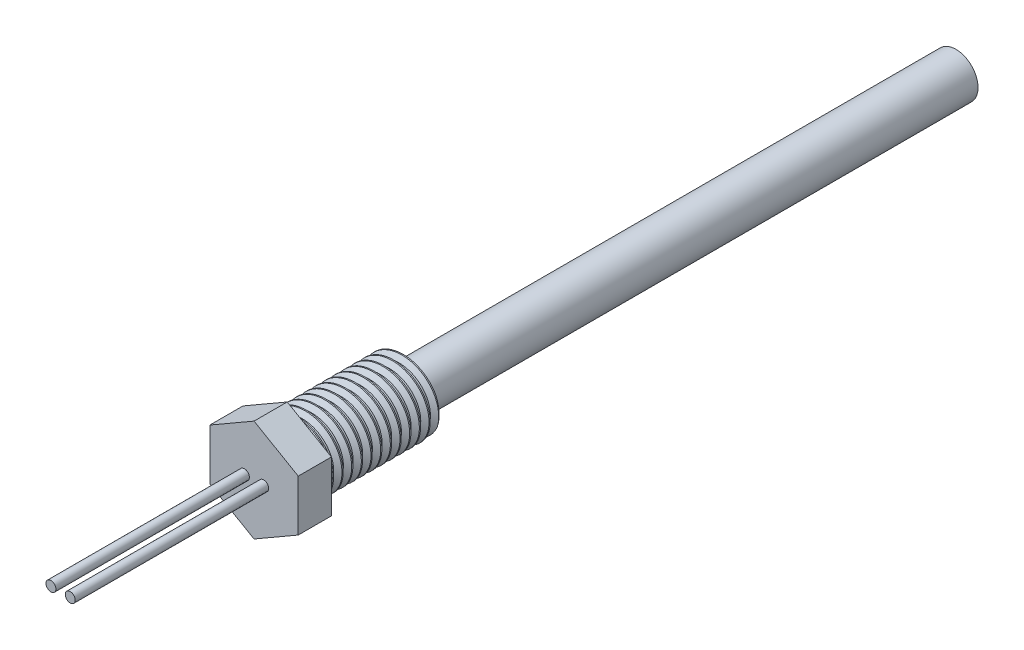
SolidWorks part; units mm, degrees
ref_plane "Ön Düzlem" through (0, 0, 0) normal (0, 0, 1) x (1, 0, 0)
ref_plane "Üst Düzlem" through (0, 0, 0) normal (0, 1, 0) x (1, 0, 0)
ref_plane "Sağ Düzlem" through (0, 0, 0) normal (1, 0, 0) x (0, 0, -1)
sketch "Çizim1" plane through (0, 0, 0) normal (0, 0, 1) x (1, 0, 0)
  circle A0 centre (0, 0) radius 4
  dimension "D1" = 8
extrude "Yükseklik-Ekstrüzyon1" add sketch "Çizim1" along normal blind 150
sketch "Çizim2" plane through (0, 0, 150) normal (0, 0, 1) x (1, 0, 0)
  circle A0 centre (0, 0) radius 6.5
  dimension "D1" = 13
extrude "Yükseklik-Ekstrüzyon2" add sketch "Çizim2" along normal blind 27
thread "Diş1" pitch 1.75 method cut profile "Diş Profili1" start angle 0, offset 0, length 30, pitch 1.75, diameter 13
ref_plane "Düzlem1" through (-6.5, 0, 177) normal (0, -1, 0) x (-1, 0, 0)
sketch "Diş Profili1" plane through (-6.5, 0, 177) normal (0, -1, 0) x (-1, 0, 0)
  line L0 (0, 0) -> (0, 1.75) construction
  line L11 (0, 0) -> (0, 1.5312)
  line L12 (0, 1.5312) -> (-0.9472, 0.9844)
  line L13 (-0.9472, 0.9844) -> (-0.9472, 0.5469)
  line L15 (-0.9472, 0.5469) -> (0, 0)
  line L17 (-0.9472, 0.7656) -> (0, 0.7656) construction
  point P2 (0, 0)
  dimension "Pitch" = 1.75
  dimension "Profile_Angle" = 60
  dimension "Profile_Land" = 0.4375
  dimension "Profile_Height" = 0.9472
sketch "Çizim3" plane through (0, 0, 0) normal (0, 0, -1) x (-1, 0, 0)
  circle A0 centre (0, 0) radius 13.0253
extrude "Kes-Ekstrüzyon1" cut sketch "Çizim3" against normal blind 50
sketch "Çizim5" plane through (0, 0, 177) normal (0, 0, 1) x (1, 0, 0)
  line L1 (0, -9.2376) -> (8, -4.6188)
  line L2 (8, -4.6188) -> (8, 4.6188)
  line L3 (8, 4.6188) -> (0, 9.2376)
  line L4 (0, 9.2376) -> (-8, 4.6188)
  line L5 (-8, 4.6188) -> (-8, -4.6188)
  line L6 (-8, -4.6188) -> (0, -9.2376)
  circle A0 centre (0, 0) radius 8 construction
  dimension "D1" = 16
extrude "Yükseklik-Ekstrüzyon4" add sketch "Çizim5" against normal blind 6
sketch "Çizim6" plane through (0, 0, 177) normal (0, 0, 1) x (1, 0, 0)
  circle A0 centre (-1.743, 0) radius 0.9
  circle A1 centre (1.743, 0) radius 0.9
  point P8 (0, 0)
  dimension "D1" = 1.8
  dimension "D2" = 1.8
extrude "Yükseklik-Ekstrüzyon5" add sketch "Çizim6" along normal blind 35
